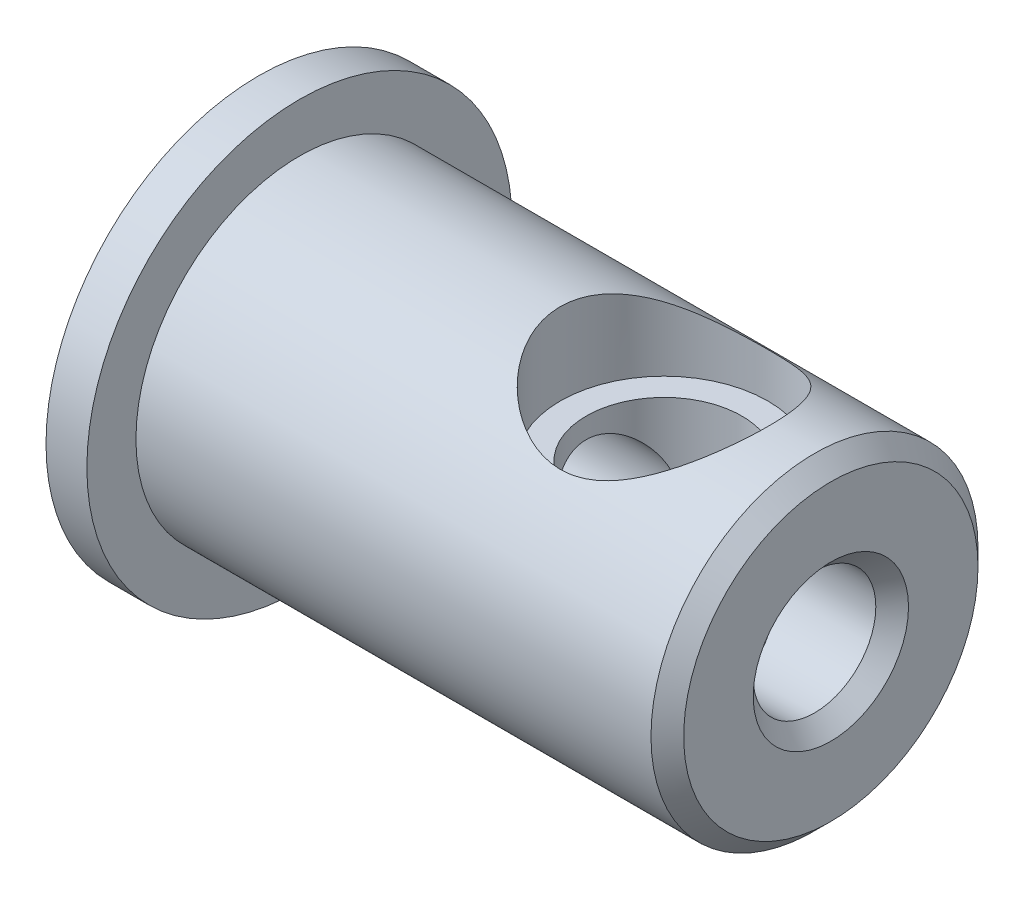
SolidWorks part; units mm, degrees
material "6061-T6 (SS)"
ref_plane "Front Plane" through (0, 0, 0) normal (0, 0, 1) x (1, 0, 0)
ref_plane "Top Plane" through (0, 0, 0) normal (0, 1, 0) x (1, 0, 0)
ref_plane "Right Plane" through (0, 0, 0) normal (1, 0, 0) x (0, 0, -1)
sketch "Sketch1" plane through (0, 0, 0) normal (1, 0, 0) x (0, 0, -1)
  circle A0 centre (0, 0) radius 13
  dimension "D1" = 26
extrude "Boss-Extrude1" add sketch "Sketch1" along normal blind 2.5
sketch "Sketch2" plane through (2.5, 0, 0) normal (1, 0, 0) x (0, 0, -1)
  circle A0 centre (0, 0) radius 10
  dimension "D1" = 20
extrude "Boss-Extrude2" add sketch "Sketch2" along normal blind 32.5
sketch "Sketch3" plane through (0, 0, 0) normal (1, 0, 0) x (0, 0, -1)
  circle A0 centre (0, 0) radius 6.25
  dimension "D1" = 12.5
sketch "Sketch4" plane through (0, 0, 0) normal (0, 1, 0) x (1, 0, 0)
  line L2 (0, 13) -> (0, -13) construction
  line L4 (0, 0) -> (24.8, 0) construction
  circle A0 centre (24.8, 0) radius 4.7625
  circle A1 centre (24.8, 0) radius 4.7625 construction
  dimension "D2" = 9.525
  dimension "D3" = 9.525
  dimension "D1" = 24.8
extrude "Cut-Extrude2" cut sketch "Sketch4" against normal mid plane 47
ref_plane "Plane1" through (0, 10, 0) normal (0, 1, 0) x (1, 0, 0)
sketch "Sketch5" plane through (0, 10, 0) normal (0, 1, 0) x (1, 0, 0)
  circle A0 centre (24.8, 0) radius 6.35
  dimension "D1" = 12.7
extrude "Cut-Extrude3" cut sketch "Sketch5" against normal blind 5
mirror "Mirror1" about plane through (0, 0, 0) normal (0, 1, 0) of "Cut-Extrude3"
extrude "Cut-Extrude4" cut sketch "Sketch3" along normal blind 15
sketch "Sketch6" plane through (15, 0, 0) normal (-1, 0, 0) x (0, 0, 1)
  circle A0 centre (0, 0) radius 3.75
  dimension "D1" = 7.5
extrude "Cut-Extrude5" cut sketch "Sketch6" against normal up to surface (20 mm away) up to face at (35, 0, -10)
chamfer "Chamfer2" distance 1 angle 45 2 edges at (35, 0, -10) (35, 0, -3.75)
